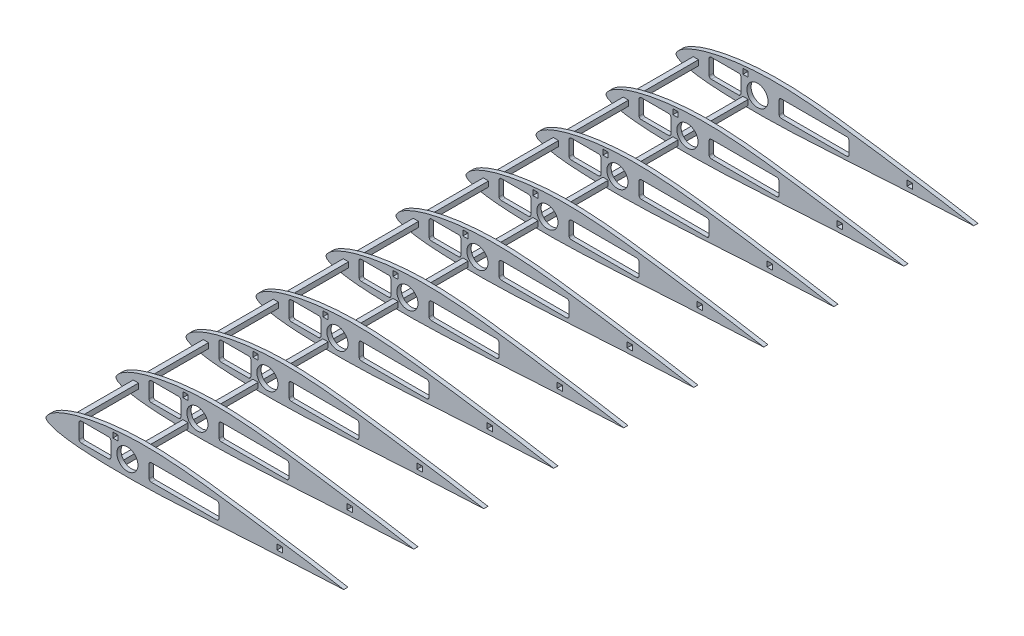
SolidWorks part; units mm, degrees
material "Balsa"
ref_plane "Front Plane" through (0, 0, 0) normal (0, 0, 1) x (1, 0, 0)
ref_plane "Top Plane" through (0, 0, 0) normal (0, 1, 0) x (1, 0, 0)
ref_plane "Right Plane" through (0, 0, 0) normal (1, 0, 0) x (0, 0, -1)
curve "Curve1"
  spline degree 3 poles (25.2088, 0.0031, 0) (25.4484, -0.0031, 0) (25.2117, 0.0209, 0) (25.0251, 0.0571, 0) (24.5852, 0.1328, 0) (24.06, 0.2322, 0) (23.3873, 0.3478, 0) (22.6018, 0.4739, 0) (21.7032, 0.6151, 0) (20.7068, 0.7694, 0) (19.6256, 0.9351, 0) (18.475, 1.1087, 0) (17.2708, 1.2865, 0) (16.0292, 1.4651, 0) (14.7666, 1.6379, 0) (13.5001, 1.8004, 0) (12.2446, 1.9439, 0) (11.0116, 2.0561, 0) (9.8099, 2.1301, 0) (8.6464, 2.1619, 0) (7.5276, 2.1493, 0) (6.459, 2.093, 0) (5.4467, 1.9949, 0) (4.4976, 1.8641, 0) (3.6202, 1.7053, 0) (2.8233, 1.523, 0) (2.1144, 1.3219, 0) (1.5008, 1.1059, 0) (0.9865, 0.8803, 0) (0.5779, 0.652, 0) (0.2708, 0.4245, 0) (0.0836, 0.2161, 0) (-0.0349, 0.004, 0) (0.089, -0.2027, 0) (0.3409, -0.3252, 0) (0.701, -0.4662, 0) (1.1913, -0.581, 0) (1.8002, -0.6841, 0) (2.5267, -0.768, 0) (3.3632, -0.8336, 0) (4.3022, -0.8807, 0) (5.334, -0.9092, 0) (6.4474, -0.9203, 0) (7.6302, -0.9134, 0) (8.8703, -0.8889, 0) (10.1572, -0.841, 0) (11.4808, -0.7741, 0) (12.8288, -0.6974, 0) (14.1854, -0.6164, 0) (15.5332, -0.5343, 0) (16.8545, -0.4545, 0) (18.1325, -0.3787, 0) (19.3501, -0.3089, 0) (20.4916, -0.2458, 0) (21.5411, -0.1904, 0) (22.4855, -0.1429, 0) (23.3092, -0.1017, 0) (24.0133, -0.0644, 0) (24.5612, -0.0287, 0) (25.0167, -0.0091, 0) (25.2088, 0.0031, 0) (25.4484, -0.0031, 0) (25.2117, 0.0209, 0) knots -0.015092 -0.006889 -0.001754 0 0.001748 0.006827 0.01488 0.025572 0.038694 0.054171 0.071834 0.091435 0.112685 0.135293 0.158944 0.183315 0.20807 0.232879 0.257399 0.281384 0.304706 0.327241 0.348897 0.369607 0.389308 0.407886 0.425177 0.441027 0.4553 0.467904 0.478752 0.487814 0.49509 0.500617 0.504451 0.507804 0.513091 0.520546 0.530249 0.542214 0.556382 0.572656 0.590895 0.610925 0.632536 0.655496 0.679547 0.704499 0.730211 0.756436 0.782837 0.809062 0.834776 0.859641 0.883338 0.905541 0.925965 0.944326 0.960366 0.973929 0.984908 0.993111 0.998246 1 1.001748 1.006827 1.01488 periodic
sketch "Sketch1" plane through (0, 0, 0) normal (0, 0, 1) x (1, 0, 0)
  line L0 (357.6496, 0) -> (0, 0) construction
  line L1 (0, 0) -> (0, 5.0209) construction
  spline S1 degree 3 poles (354.9573, 0.0431) (358.3317, -0.0432) (354.9981, 0.2938) (352.3707, 0.8024) (346.1763, 1.8676) (338.7813, 3.2655) (329.3081, 4.8919) (318.2482, 6.6648) (305.5952, 8.6507) (291.564, 10.8193) (276.34, 13.1505) (260.1392, 15.5903) (243.1815, 18.0913) (225.699, 20.6027) (207.9209, 23.0318) (190.087, 25.3152) (172.4086, 27.3328) (155.0467, 28.9096) (138.1258, 29.947) (121.7437, 30.3922) (105.9899, 30.2108) (90.9433, 29.4155) (76.6903, 28.0308) (63.3272, 26.1868) (50.9728, 23.9485) (39.7523, 21.3791) (29.7714, 18.545) (21.1318, 15.5018) (13.8914, 12.3237) (8.1391, 9.1075) (3.8158, 5.9031) (1.1802, 2.9693) (-0.4877, -0.018) (1.2572, -2.9285) (4.805, -4.6528) (9.8754, -6.6365) (16.78, -8.2511) (25.3535, -9.7017) (35.5828, -10.8813) (47.3622, -11.8027) (60.5842, -12.4624) (75.1117, -12.8607) (90.7897, -13.0132) (107.4435, -12.9137) (124.9052, -12.5651) (143.0256, -11.8868) (161.6617, -10.9405) (180.6424, -9.8572) (199.7442, -8.7119) (218.721, -7.5525) (237.3263, -6.4253) (255.3201, -5.3536) (272.4652, -4.367) (288.5372, -3.4753) (303.3148, -2.6922) (316.6121, -2.0207) (328.2104, -1.4385) (338.1246, -0.9102) (345.8395, -0.4061) (352.2525, -0.129) (354.9573, 0.0431) (358.3317, -0.0432) (354.9981, 0.2938) knots -0.015092 -0.006889 -0.001754 0 0.001748 0.006827 0.01488 0.025572 0.038694 0.054171 0.071834 0.091435 0.112685 0.135293 0.158944 0.183315 0.20807 0.232879 0.257399 0.281384 0.304706 0.327241 0.348897 0.369607 0.389308 0.407886 0.425177 0.441027 0.4553 0.467904 0.478752 0.487814 0.49509 0.500617 0.504451 0.507804 0.513091 0.520546 0.530249 0.542214 0.556382 0.572656 0.590895 0.610925 0.632536 0.655496 0.679547 0.704499 0.730211 0.756436 0.782837 0.809062 0.834776 0.859641 0.883338 0.905541 0.925965 0.944326 0.960366 0.973929 0.984908 0.993111 0.998246 1 1.001748 1.006827 1.01488 only from (357.6496, 0) to (357.6496, 0)
  dimension "D1" = 357.6496
extrude "Boss-Extrude2" add sketch "Sketch1" along normal blind 5.08 contours S1
sketch "Sketch14" plane through (0, 0, 0) normal (0, 0, -1) x (-1, 0, 0)
  line L1 (-126.3762, 16.4077) -> (-205.1162, 16.4077)
  line L2 (-123.8362, 13.8677) -> (-123.8362, -1.3723)
  line L3 (-126.3762, -3.9123) -> (-205.1162, -3.9123)
  line L4 (-207.6562, 13.8677) -> (-207.6562, -1.3723)
  line L5 (-75.2852, 17.6777) -> (-42.2652, 17.6777)
  line L6 (-77.8252, 15.1377) -> (-77.8252, -2.6423)
  line L7 (-75.2852, -5.1823) -> (-42.2652, -5.1823)
  line L8 (-39.7252, 15.1377) -> (-39.7252, -2.6423)
  circle A0 centre (-97.7699, 5.7638) radius 12.7
  arc A1 (-77.8252, -2.6423) -> (-75.2852, -5.1823) centre (-75.2852, -2.6423) ccw
  arc A2 (-42.2652, -5.1823) -> (-39.7252, -2.6423) centre (-42.2652, -2.6423) ccw
  arc A3 (-42.2652, 17.6777) -> (-39.7252, 15.1377) centre (-42.2652, 15.1377) cw
  arc A4 (-75.2852, 17.6777) -> (-77.8252, 15.1377) centre (-75.2852, 15.1377) ccw
  arc A5 (-205.1162, -3.9123) -> (-207.6562, -1.3723) centre (-205.1162, -1.3723) cw
  arc A6 (-123.8362, -1.3723) -> (-126.3762, -3.9123) centre (-126.3762, -1.3723) cw
  arc A7 (-126.3762, 16.4077) -> (-123.8362, 13.8677) centre (-126.3762, 13.8677) cw
  arc A8 (-205.1162, 16.4077) -> (-207.6562, 13.8677) centre (-205.1162, 13.8677) ccw
  point P13 (-77.8252, -5.1823)
  point P16 (-39.7252, -5.1823)
  point P21 (-77.8252, 17.6777)
  point P24 (-207.6562, -3.9123)
  point P27 (-123.8362, -3.9123)
  point P30 (-123.8362, 16.4077)
  dimension "D1" = 25.4
  dimension "D7" = 2.54
  dimension "D2" = 20.32
  dimension "D3" = 22.86
  dimension "D4" = 1.27
  dimension "D5" = 38.1
  dimension "D6" = 83.82
extrude "Cut-Extrude2" cut sketch "Sketch14" against normal up to surface (5.08 mm away)
sketch "Sketch15" plane through (0, 0, 0) normal (0, 0, -1) x (-1, 0, 0)
  line L0 (-207.6562, 13.8677) -> (-207.6562, -1.3723) construction
  line L1 (-283.8562, 7.5177) -> (-277.5062, 7.5177)
  line L2 (-283.8562, 7.5177) -> (-283.8562, 1.0492)
  line L3 (-283.8562, 1.0492) -> (-277.5062, 1.0492)
  line L4 (-277.5062, 7.5177) -> (-277.5062, 1.0492)
  line L5 (-126.3762, 16.4077) -> (-205.1162, 16.4077) construction
  line L6 (-39.7252, -2.6423) -> (-39.7252, 15.1377) construction
  line L7 (-27.0252, 7.5177) -> (-20.6752, 7.5177)
  line L8 (-27.0252, 7.5177) -> (-27.0252, 1.1677)
  line L9 (-27.0252, 1.1677) -> (-20.6752, 1.1677)
  line L10 (-20.6752, 7.5177) -> (-20.6752, 1.1677)
  line L11 (-42.2652, 17.6777) -> (-75.2852, 17.6777) construction
  line L12 (-86.7152, 25.2977) -> (-80.3652, 25.2977)
  line L13 (-86.7152, 25.2977) -> (-86.7152, 18.9477)
  line L14 (-86.7152, 18.9477) -> (-80.3652, 18.9477)
  line L15 (-80.3652, 25.2977) -> (-80.3652, 18.9477)
  line L16 (-77.8252, 15.1377) -> (-77.8252, -2.6423) construction
  line L18 (-86.7152, -3.9123) -> (-80.3652, -3.9123)
  line L19 (-86.7152, -3.9123) -> (-86.7152, -10.2623)
  line L20 (-86.7152, -10.2623) -> (-80.3652, -10.2623)
  line L21 (-80.3652, -3.9123) -> (-80.3652, -10.2623)
  point P20 (-80.3652, 22.1227)
  dimension "D1" = 6.35
  dimension "D2" = 6.4685
  dimension "D3" = 76.2
  dimension "D4" = 8.89
  dimension "D5" = 6.35
  dimension "D6" = 6.35
  dimension "D7" = 12.7
  dimension "D8" = 0
  dimension "D9" = 6.35
  dimension "D10" = 6.35
  dimension "D11" = 1.27
  dimension "D12" = 2.54
  dimension "D13" = 6.35
  dimension "D14" = 6.35
  dimension "D15" = 2.54
  dimension "D16" = 22.86
extrude "Cut-Extrude3" cut sketch "Sketch15" against normal up to next
pattern_linear "LPattern3" count 10 spacing 84.1022 along (0, 0, 1) of bodies 135
sketch "Sketch16" plane through (0, 0, 0) normal (0, 0, -1) x (-1, 0, 0)
  line L1 (-86.7152, -10.2623) -> (-80.3652, -10.2623)
  line L2 (-86.7152, -10.2623) -> (-86.7152, -3.9123)
  line L3 (-86.7152, -3.9123) -> (-80.3652, -3.9123)
  line L4 (-80.3652, -10.2623) -> (-80.3652, -3.9123)
  line L5 (-27.0252, 1.1677) -> (-20.6752, 1.1677)
  line L6 (-27.0252, 1.1677) -> (-27.0252, 7.5177)
  line L7 (-27.0252, 7.5177) -> (-20.6752, 7.5177)
  line L8 (-20.6752, 1.1677) -> (-20.6752, 7.5177)
extrude "Boss-Extrude14" add sketch "Sketch16" against normal through all
